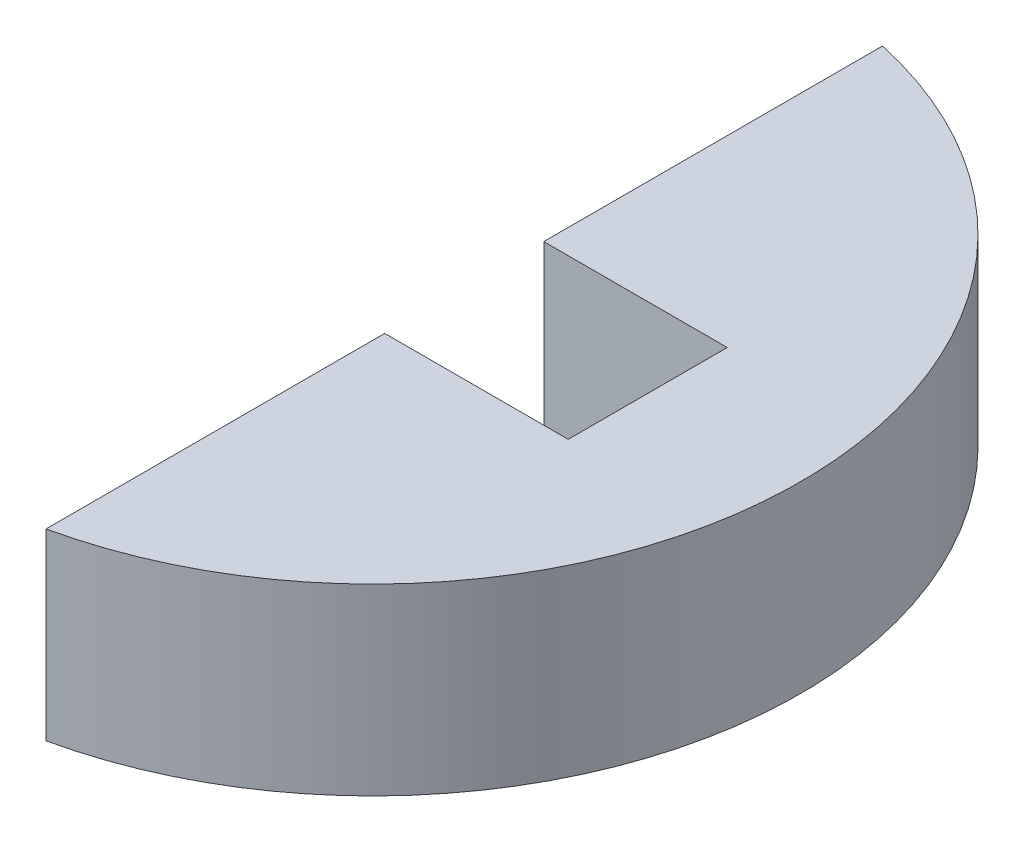
SolidWorks part; units mm, degrees
ref_plane "Front Plane" through (0, 0, 0) normal (0, 0, 1) x (1, 0, 0)
ref_plane "Top Plane" through (0, 0, 0) normal (0, 1, 0) x (1, 0, 0)
ref_plane "Right Plane" through (0, 0, 0) normal (1, 0, 0) x (0, 0, -1)
sketch "Sketch1" plane through (0, 0, 0) normal (0, 1, 0) x (1, 0, 0)
  line L0 (1.5, -6.8374) -> (1.5, -1.3)
  line L1 (1.5, -1.3) -> (4.5, -1.3)
  line L2 (4.5, -1.3) -> (4.5, 1.3)
  line L3 (4.5, 1.3) -> (1.5, 1.3)
  line L4 (1.5, 1.3) -> (1.5, 6.8374)
  line L6 (-1.5, 0) -> (1.5, 0) construction
  line L7 (-1.5, 0) -> (1.5, 0) construction
  line L8 (-7, 0) -> (7, 0) construction
  line L9 (-7, 0) -> (7, 0) construction
  line L10 (0, -7) -> (0, 7) construction
  arc A0 (1.5, -6.8374) -> (1.5, 6.8374) centre (0, 0) ccw
  point P7 (4.5, 0)
  point P8 (0, 0)
  dimension "D1" = 2.6
extrude "Boss-Extrude1" add sketch "Sketch1" along normal blind 1.5 and the other way blind 1.5
